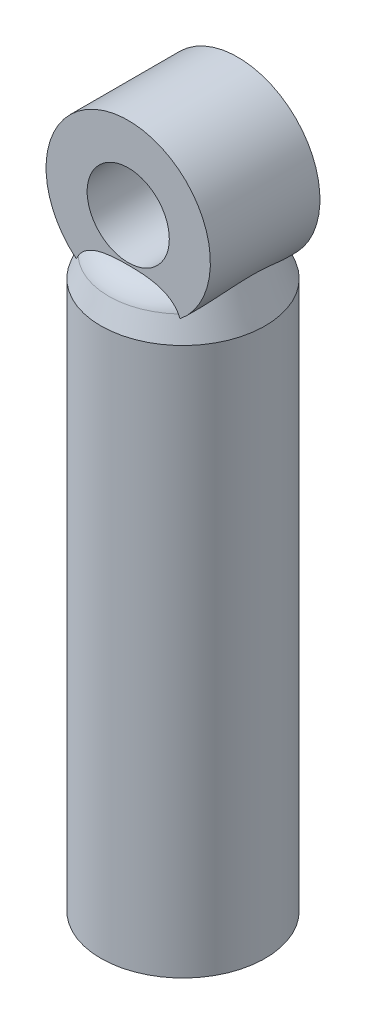
SolidWorks part; units mm, degrees
ref_plane "Front Plane" through (0, 0, 0) normal (0, 0, 1) x (1, 0, 0)
ref_plane "Top Plane" through (0, 0, 0) normal (0, 1, 0) x (1, 0, 0)
ref_plane "Right Plane" through (0, 0, 0) normal (1, 0, 0) x (0, 0, -1)
sketch "Sketch1" plane through (0, 0, 0) normal (0, 1, 0) x (1, 0, 0)
  circle A0 centre (0, 0) radius 3
  circle A1 centre (0, 0) radius 1.5
  dimension "D1" = 6
  dimension "D2" = 3
extrude "Boss-Extrude1" add sketch "Sketch1" along normal blind 20
sketch "Sketch2" plane through (0, 0, 0) normal (0, 0, 1) x (1, 0, 0)
  line L0 (3, 20) -> (-3, 20) construction
  circle A0 centre (0, 23) radius 3
  circle A1 centre (0, 23) radius 1.5
  dimension "D1" = 6
  dimension "D2" = 3
extrude "Boss-Extrude2" add sketch "Sketch2" along normal mid plane 4 separate body
ref_plane "Plane1" through (0, 23, 0) normal (0, 1, 0) x (1, 0, 0)
sketch "Sketch3" plane through (0, 23, 0) normal (0, 1, 0) x (1, 0, 0)
  line L0 (-3, -2) -> (-3, 2)
  line L1 (-3, 2) -> (3, 2)
  line L2 (3, 2) -> (3, -2)
  line L3 (3, -2) -> (-3, -2)
sketch "Sketch4" plane through (0, 20, 0) normal (0, 1, 0) x (1, 0, 0)
  circle A1 centre (0, 0) radius 3
  circle A2 centre (0, 0) radius 3
  dimension "D1" = 0
extrude "Boss-Extrude3" add sketch "Sketch4" along normal blind 1.45 draft 20
fillet "Fillet1" radius 1 2 edges at (0, 21.45, -2.4722) (0, 21.45, 2.4722)
